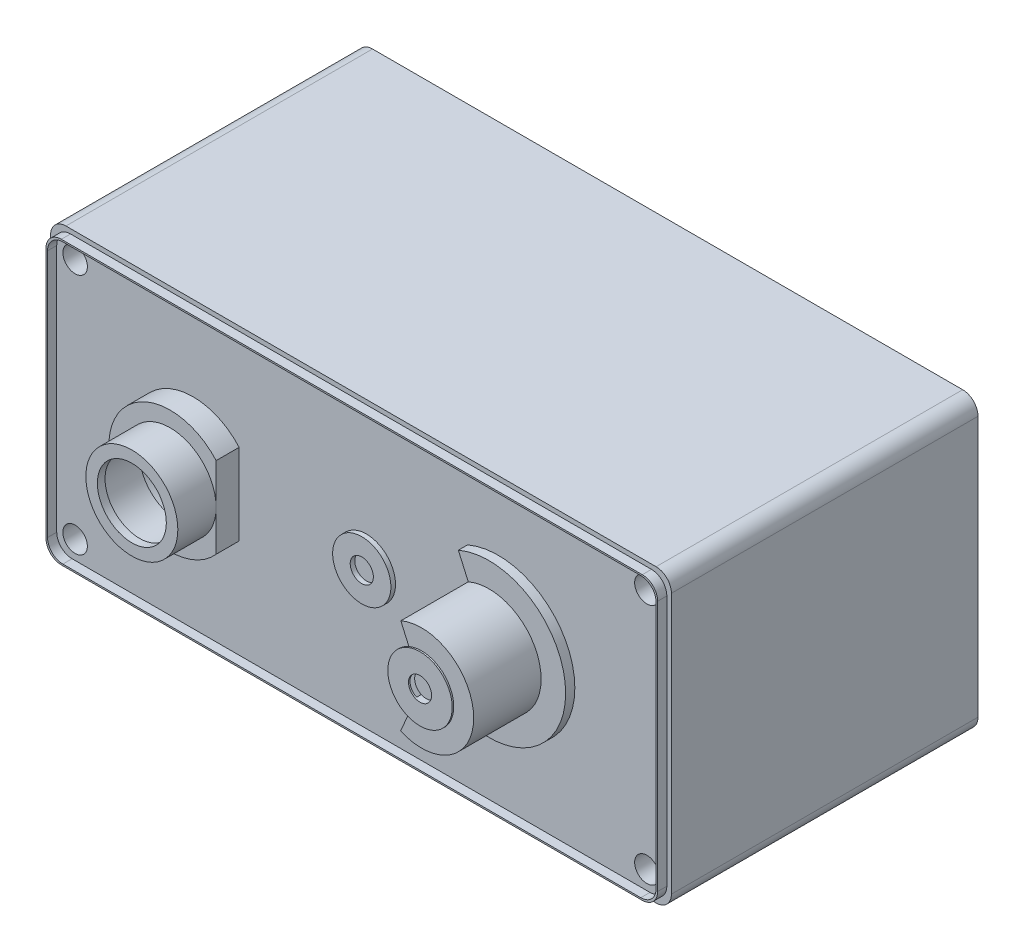
SolidWorks part; units mm, degrees
material "ABS"
ref_plane "Alzado" through (0, 0, 0) normal (0, 0, 1) x (1, 0, 0)
ref_plane "Planta" through (0, 0, 0) normal (0, 1, 0) x (1, 0, 0)
ref_plane "Vista lateral" through (0, 0, 0) normal (1, 0, 0) x (0, 0, -1)
sketch "Croquis1" plane through (0, 0, 0) normal (0, 0, 1) x (1, 0, 0)
  line L0 (-20.25, 8.5) -> (-20.25, -8.5)
  line L1 (-19.25, -9.5) -> (19.25, -9.5)
  line L2 (20.25, -8.5) -> (20.25, 8.5)
  line L3 (19.25, 9.5) -> (-19.25, 9.5)
  line L4 (0, -9.5) -> (0, 9.5) construction
  line L5 (20.25, 0) -> (-20.25, 0) construction
  arc A0 (20.25, 8.5) -> (19.25, 9.5) centre (19.25, 8.5) ccw
  arc A1 (19.25, -9.5) -> (20.25, -8.5) centre (19.25, -8.5) ccw
  arc A2 (-20.25, 8.5) -> (-19.25, 9.5) centre (-19.25, 8.5) cw
  arc A3 (-20.25, -8.5) -> (-19.25, -9.5) centre (-19.25, -8.5) ccw
  circle A4 centre (18.65, -7.9) radius 0.8
  circle A5 centre (-18.65, -7.9) radius 0.8
  circle A6 centre (-18.65, 7.9) radius 0.8
  circle A7 centre (18.65, 7.9) radius 0.8
  point P4 (-20.25, 0)
  point P5 (0, -9.5)
  point P6 (20.25, 0)
  point P7 (0, 9.5)
  dimension "D1" = 1
  dimension "D4" = 1.6
  dimension "D2" = 19
  dimension "D3" = 40.5
  dimension "D5" = 1.6
  dimension "D6" = 1.6
extrude "Saliente-Extruir1" add sketch "Croquis1" along normal blind 20
sketch "Croquis2" plane through (0, 0, 20) normal (0, 0, 1) x (1, 0, 0)
  line L0 (18.95, -9.2) -> (-18.95, -9.2)
  line L1 (-19.95, -8.2) -> (-19.95, 8.2)
  line L2 (-18.95, 9.2) -> (18.95, 9.2)
  line L3 (19.95, 8.2) -> (19.95, -8.2)
  line L4 (-19.25, -9.5) -> (19.25, -9.5) construction
  line L5 (-20.25, 8.5) -> (-20.25, -8.5) construction
  line L6 (19.25, 9.5) -> (-19.25, 9.5) construction
  line L7 (20.25, -8.5) -> (20.25, 8.5) construction
  line L8 (18.85, -9.1) -> (-18.85, -9.1)
  line L9 (-19.85, -8.1) -> (-19.85, 8.1)
  line L10 (-18.85, 9.1) -> (18.85, 9.1)
  line L15 (19.85, 8.1) -> (19.85, -8.1)
  arc A1 (-18.95, -9.2) -> (-19.95, -8.2) centre (-18.95, -8.2) cw
  arc A2 (-19.95, 8.2) -> (-18.95, 9.2) centre (-18.95, 8.2) cw
  arc A3 (18.95, 9.2) -> (19.95, 8.2) centre (18.95, 8.2) cw
  arc A4 (18.95, -9.2) -> (19.95, -8.2) centre (18.95, -8.2) ccw
  arc A5 (-18.85, -9.1) -> (-19.85, -8.1) centre (-18.85, -8.1) cw
  arc A6 (-19.85, 8.1) -> (-18.85, 9.1) centre (-18.85, 8.1) cw
  arc A7 (18.85, 9.1) -> (19.85, 8.1) centre (18.85, 8.1) cw
  arc A8 (18.85, -9.1) -> (19.85, -8.1) centre (18.85, -8.1) ccw
  dimension "D5" = 1
  dimension "D6" = 1
  dimension "D1" = 0.3
  dimension "D2" = 0.3
  dimension "D3" = 0.3
  dimension "D4" = 0.3
  dimension "D7" = 0.1
  dimension "D8" = 0.1
  dimension "D9" = 0.1
  dimension "D10" = 0.1
extrude "Saliente-Extruir2" add sketch "Croquis2" along normal blind 0.6
sketch "Croquis3" plane through (0, 0, 20) normal (0, 0, 1) x (1, 0, 0)
  line L0 (-7.95, -2.6458) -> (-7.95, 2.6458)
  line L1 (-19.95, 8.2) -> (-19.95, -8.2) construction
  line L2 (6.95, 4.5826) -> (6.95, -4.5826)
  line L3 (19.95, -8.2) -> (19.95, 8.2) construction
  arc A0 (-7.95, 2.6458) -> (-7.95, -2.6458) centre (-10.95, 0) ccw
  arc A1 (6.95, -4.5826) -> (6.95, 4.5826) centre (8.95, 0) ccw
  circle A2 centre (0.35, 0) radius 1.9
  circle A3 centre (0.35, 0) radius 0.755
  circle A4 centre (-10.95, 0) radius 3
  arc A5 (6.95, -2.7495) -> (6.95, 2.7495) centre (8.95, 0) ccw
  point P4 (-14.95, 0)
  point P11 (13.95, 0)
  point P13 (-1.55, 0)
  dimension "D1" = 8
  dimension "D4" = 10
  dimension "D7" = 15.5
  dimension "D8" = 3.8
  dimension "D9" = 1.51
  dimension "D10" = 6
  dimension "D11" = 6.8
  dimension "D2" = 7
  dimension "D3" = 12
  dimension "D5" = 7
  dimension "D6" = 13
extrude "Saliente-Extruir3" add sketch "Croquis3" along normal blind 0.3 contours A2 A3 region at (-1.4963, 0, 20)
extrude "Saliente-Extruir5" add sketch "Croquis3<3>" along normal blind 0.6 contours L2 A5 | A5 L2 A1 region at (13.8279, 0, 20) region at (9.3981, 0, 20)
sketch "Croquis3<3>" plane through (0, 0, 20) normal (0, 0, 1) x (1, 0, 0) same geometry as "Croquis3"
extrude "Saliente-Extruir6" add sketch "Croquis3<4>" along normal blind 1.5 contours L0 A4 A0 | A4 region at (-10.95, 0, 20) region at (-14.8437, 0, 20)
sketch "Croquis3<4>" plane through (0, 0, 20) normal (0, 0, 1) x (1, 0, 0) same geometry as "Croquis3"
extrude "Saliente-Extruir7" add sketch "Croquis3<5>" along normal blind 4 contours A4
sketch "Croquis3<5>" plane through (0, 0, 20) normal (0, 0, 1) x (1, 0, 0) same geometry as "Croquis3"
extrude "Saliente-Extruir8" add sketch "Croquis3<8>" along normal blind 5 contours L2 A5 region at (9.3981, 0, 20)
sketch "Croquis3<8>" plane through (0, 0, 20) normal (0, 0, 1) x (1, 0, 0) same geometry as "Croquis3"
shell "Vaciado1" thickness 0.5 removed face at (0, 0, 0)
sketch "Croquis6" plane through (0, 0, 24) normal (0, 0, 1) x (1, 0, 0)
  circle A0 centre (-10.95, 0) radius 2.25
  dimension "D1" = 4.5
extrude "Cortar-Extruir1" cut sketch "Croquis6" against normal blind 5
sketch "Croquis7" plane through (0, 0, 25) normal (0, 0, 1) x (1, 0, 0)
  circle A0 centre (8.95, 0) radius 2.1
  circle A1 centre (8.95, 0) radius 0.755
  dimension "D1" = 4.2
  dimension "D2" = 1.51
extrude "Saliente-Extruir9" add sketch "Croquis7" along normal blind 0.1
extrude "Cortar-Extruir2" cut sketch "Croquis7<2>" against normal blind 0.3 contours A1 region at (8.95, 0, 25)
sketch "Croquis7<2>" plane through (0, 0, 25) normal (0, 0, 1) x (1, 0, 0) same geometry as "Croquis7"
sketch "Croquis9" plane through (6.95, 0, 0) normal (-1, 0, 0) x (0, 0, 1)
  line L0 (24.9, 2.3495) -> (20, 2.3495)
  line L2 (20, 4.5826) -> (20, -4.5826) construction
  line L3 (20, 2.3495) -> (20, -2.3495)
  line L4 (20, -2.3495) -> (24.9, -2.3495)
  line L6 (24.9, -2.3495) -> (24.9, 2.3495)
  line L7 (25, -2.7495) -> (20.6, -2.7495) construction
  line L8 (25, 2.7495) -> (20.6, 2.7495) construction
  point P2 (288.0684, -33.6727)
  point P8 (22.8, -2.7495)
  dimension "D1" = 4.9
  dimension "D2" = 0.4
  dimension "D3" = 0.4
extrude "Cortar-Extruir3" cut sketch "Croquis9" against normal blind 1.2
sketch "Croquis10" plane through (0, 0, 20) normal (0, 0, 1) x (1, 0, 0)
  line L0 (8.6704, 0.696) -> (6.95, 4.5826)
  line L1 (8.6298, -0.6782) -> (6.95, -4.5826)
  line L2 (6.95, -4.5826) -> (6.95, 4.5826)
  arc A0 (8.6704, 0.696) -> (8.6298, -0.6782) centre (8.95, 0) ccw
  dimension "D1" = 0.75
  dimension "D2" = 3.9044
extrude "Cortar-Extruir4" cut sketch "Croquis10" along normal blind 5
